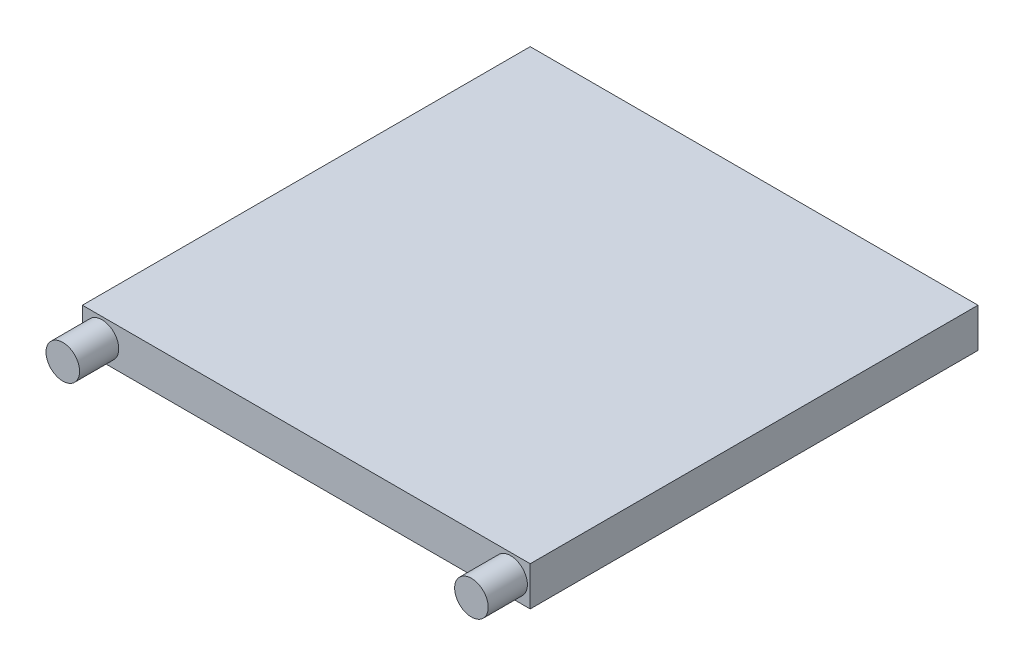
SolidWorks part; units mm, degrees
ref_plane "Front Plane" through (0, 0, 0) normal (0, 0, 1) x (1, 0, 0)
ref_plane "Top Plane" through (0, 0, 0) normal (0, 1, 0) x (1, 0, 0)
ref_plane "Right Plane" through (0, 0, 0) normal (1, 0, 0) x (0, 0, -1)
sketch "Sketch1" plane through (0, 0, 0) normal (0, 1, 0) x (1, 0, 0)
  line L1 (-20, -20) -> (20, -20)
  line L2 (-20, -20) -> (-20, 20)
  line L3 (-20, 20) -> (20, 20)
  line L4 (20, -20) -> (20, 20)
  line L5 (-20, -20) -> (20, 20) construction
  line L6 (-20, 20) -> (20, -20) construction
  point P0 (0, 0)
  dimension "D1" = 40
  dimension "D2" = 40
extrude "Boss-Extrude1" add sketch "Sketch1" along normal blind 3.5
sketch "Sketch2" plane through (0, 0, 20) normal (0, 0, 1) x (1, 0, 0)
  line L0 (-20, 3.5) -> (-20, 0) construction
  line L1 (-20, 0) -> (20, 0) construction
  line L2 (0, 0) -> (0, 3.5)
  line L3 (-20, 3.5) -> (20, 3.5) construction
  circle A0 centre (-18.25, 1.75) radius 1.5
  circle A1 centre (18.25, 1.75) radius 1.5
  dimension "D3" = 3
  dimension "D1" = 1.75
  dimension "D2" = 1.75
extrude "Boss-Extrude2" add sketch "Sketch2" along normal blind 3.5 contours A1 | A0 region at (-18.25, 1.75, 20) region at (18.25, 1.75, 20)
